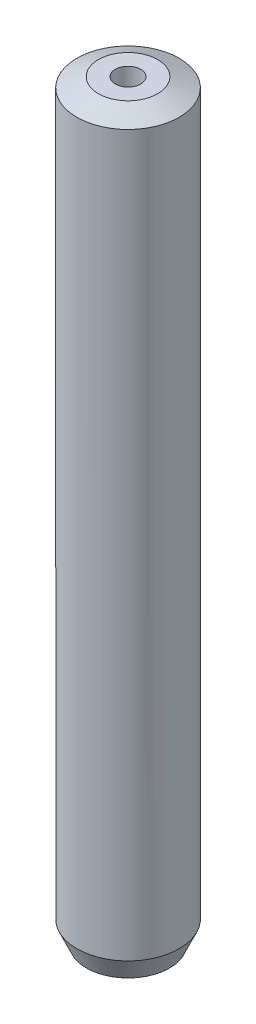
SolidWorks part; units mm, degrees
ref_plane "Front Plane" through (0, 0, 0) normal (0, 0, 1) x (1, 0, 0)
ref_plane "Top Plane" through (0, 0, 0) normal (0, 1, 0) x (1, 0, 0)
ref_plane "Right Plane" through (0, 0, 0) normal (1, 0, 0) x (0, 0, -1)
sketch "Sketch1" plane through (0, 0, 0) normal (0, 1, 0) x (1, 0, 0)
  circle A0 centre (0, 0) radius 7.5
  dimension "SHAFT_OD" = 15
extrude "Boss-Extrude1" add sketch "Sketch1" along normal blind 110.1104
sketch "Sketch2" plane through (0, 0, 0) normal (0, 1, 0) x (1, 0, 0)
  circle A0 centre (0, 0) radius 1.8686
  dimension "BORE_D" = 3.7372
extrude "Cut-Extrude1" cut sketch "Sketch2" along normal through all
chamfer "Chamfer1" distance 1.4073 angle 66.005 2 edges at (0, 110.1104, 7.5) (0, 0, 7.5) first distance on face at (0, 110.1104, 7.5) first distance on face at (0, 0, 1.8686)
